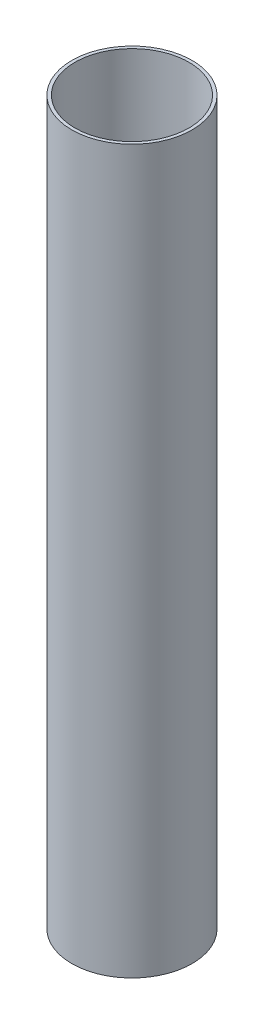
SolidWorks part; units mm, degrees
ref_plane "Front Plane" through (0, 0, 0) normal (0, 0, 1) x (1, 0, 0)
ref_plane "Top Plane" through (0, 0, 0) normal (0, 1, 0) x (1, 0, 0)
ref_plane "Right Plane" through (0, 0, 0) normal (1, 0, 0) x (0, 0, -1)
sketch "Sketch1" plane through (0, 0, 0) normal (0, 1, 0) x (1, 0, 0)
  circle A0 centre (0, 0) radius 36.1
  circle A1 centre (0, 0) radius 38.1
  dimension "D1" = 2
  dimension "D2" = 76.2
extrude "Boss-Extrude1" add sketch "Sketch1" along normal blind 457.2
